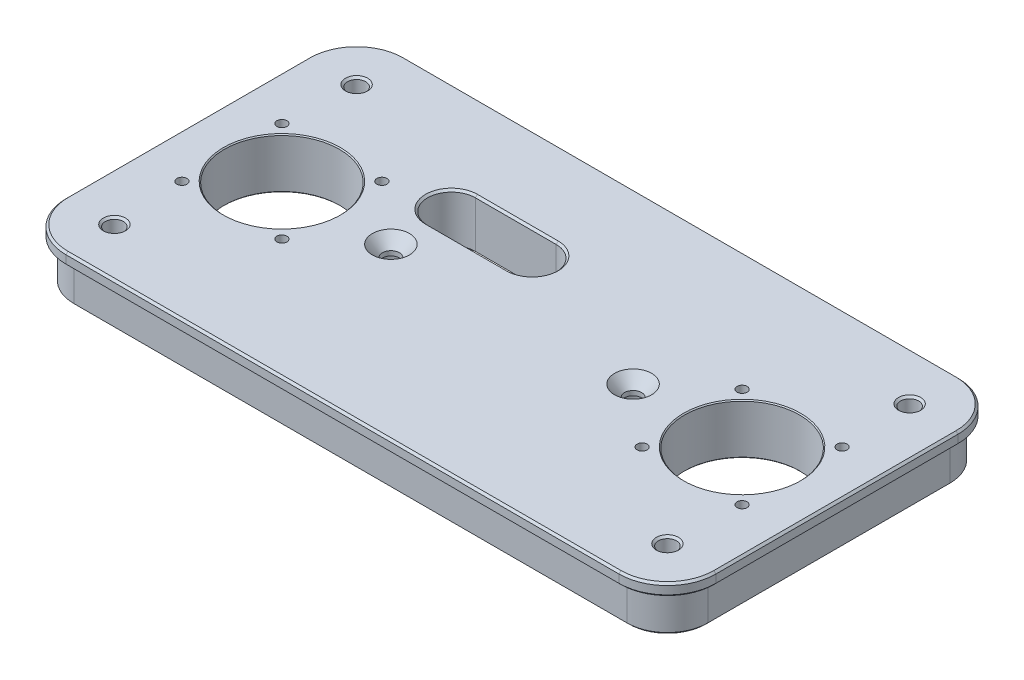
SolidWorks part; units mm, degrees
material "6061-T6 Aluminum"
ref_plane "Front Plane" through (0, 0, 0) normal (0, 0, 1) x (1, 0, 0)
ref_plane "Top Plane" through (0, 0, 0) normal (0, 1, 0) x (1, 0, 0)
ref_plane "Right Plane" through (0, 0, 0) normal (1, 0, 0) x (0, 0, -1)
sketch "Sketch1" plane through (0, 0, 0) normal (0, 1, 0) x (1, 0, 0)
  line L1 (-157, -80) -> (157, -80)
  line L2 (-157, -80) -> (-157, 80)
  line L3 (-157, 80) -> (157, 80)
  line L4 (157, -80) -> (157, 80)
  line L5 (-157, -80) -> (157, 80) construction
  line L6 (-157, 80) -> (157, -80) construction
  point P0 (0, 0)
  dimension "D1" = 160
  dimension "D2" = 314
extrude "Boss-Extrude1" add sketch "Sketch1" along normal blind 25
sketch "Sketch2" plane through (0, 25, 0) normal (0, 1, 0) x (1, 0, 0)
  line L0 (-114, 0) -> (0, 0) construction
  line L1 (0, 0) -> (114, 0) construction
  circle A0 centre (-114, 0) radius 28.5
  circle A1 centre (114, 0) radius 28.5
  dimension "D1" = 228
  dimension "D2" = 57
extrude "Cut-Extrude1" cut sketch "Sketch2" against normal through all
sketch "Sketch4" plane through (0, 25, 0) normal (0, 1, 0) x (1, 0, 0)
  line L0 (60, 0) -> (0, 0) construction
  line L1 (0, 0) -> (-60, 0) construction
  circle A0 centre (-60, 0) radius 9.55
  circle A1 centre (60, 0) radius 9.55
  dimension "D1" = 19.1
  dimension "D2" = 120
extrude "Cut-Extrude2" cut sketch "Sketch4" against normal through all both and the other way through all
chamfer "Chamfer1" distance 0.5 angle 45 8 edges at (114, 25, 28.5) (114, 0, 28.5) (60, 25, -9.55) (60, 0, 9.55) (-60, 25, -9.55) (-60, 0, 9.55) (-114, 25, 28.5) (-114, 0, 28.5)
fillet "Fillet1" radius 20 4 edges at (157, 12.5, 80) (157, 12.5, -80) (-157, 12.5, -80) (-157, 12.5, 80)
hole_wizard "M8 Clearance Hole1" positions "Sketch5" profile "Sketch6" hole size "M8" standard "ANSI Metric" end condition through all
sketch "Sketch5" plane through (0, 0, 0) normal (0, 1, 0) x (1, 0, 0)
  point P0 (-137, 60)
  point P3 (-137, -60)
  point P6 (137, 60)
  point P9 (137, -60)
sketch "Sketch6" plane through (-137, 0, -60) normal (1, 0, 0) x (0, 0, -1)
  line L0 (0, 0) -> (0, 25)
  line L1 (0, 25) -> (4.5, 25)
  line L2 (4.5, 25) -> (4.5, 0)
  line L5 (4.5, 0) -> (0, 0)
  line L11 (0, -6.35) -> (0, 107.95) construction
  dimension "Thru Hole Dia." = 9
  dimension "Thru Hole Depth" = 25
sketch "Sketch7" plane through (0, 0, 0) normal (0, -1, 0) x (1, 0, 0)
  line L1 (89.235, 24.765) -> (138.765, 24.765) construction
  line L2 (89.235, 24.765) -> (89.235, -24.765) construction
  line L3 (89.235, -24.765) -> (138.765, -24.765) construction
  line L4 (138.765, 24.765) -> (138.765, -24.765) construction
  line L5 (89.235, 24.765) -> (138.765, -24.765) construction
  line L6 (89.235, -24.765) -> (138.765, 24.765) construction
  line L7 (-138.765, 24.765) -> (-89.235, 24.765) construction
  line L8 (-138.765, 24.765) -> (-138.765, -24.765) construction
  line L9 (-138.765, -24.765) -> (-89.235, -24.765) construction
  line L10 (-89.235, 24.765) -> (-89.235, -24.765) construction
  line L11 (-138.765, 24.765) -> (-89.235, -24.765) construction
  line L12 (-138.765, -24.765) -> (-89.235, 24.765) construction
  circle A0 centre (89.235, 24.765) radius 3.302 construction
  circle A1 centre (138.765, -24.765) radius 3.302 construction
  circle A2 centre (138.765, 24.765) radius 3.302 construction
  circle A3 centre (89.235, -24.765) radius 3.302 construction
  circle A4 centre (89.235, 24.765) radius 3.302
  circle A5 centre (138.765, -24.765) radius 3.302
  circle A6 centre (138.765, 24.765) radius 3.302
  circle A7 centre (89.235, -24.765) radius 3.302
  circle A12 centre (-138.765, -24.765) radius 3.302
  circle A13 centre (-89.235, -24.765) radius 3.302
  circle A14 centre (-89.235, 24.765) radius 3.302
  circle A15 centre (-138.765, 24.765) radius 3.302
  point P13 (114, 0)
  point P15 (-114, 0)
hole_wizard "M6x1.0 Tapped Hole1" positions "Sketch8" profile "Sketch9" tap size "M6x1.0" standard "ANSI Metric" end condition through all
sketch "Sketch8" plane through (0, 0, 0) normal (0, -1, 0) x (-1, 0, 0)
  point P0 (138.765, -24.765)
  point P3 (89.235, -24.765)
  point P6 (89.235, 24.765)
  point P9 (138.765, 24.765)
  point P12 (-89.235, -24.765)
  point P15 (-138.765, -24.765)
  point P18 (-89.235, 24.765)
  point P21 (-138.765, 24.765)
cosmetic thread "Hole Thread11" parameters "D2"=6
cosmetic thread "Hole Thread12" parameters "D2"=6
cosmetic thread "Hole Thread13" parameters "D2"=6
cosmetic thread "Hole Thread14" parameters "D2"=6
cosmetic thread "Hole Thread16" parameters "D2"=6
sketch "Sketch9" plane through (-138.765, 0, 24.765) normal (1, 0, 0) x (0, 0, -1)
  line L0 (0, 0) -> (0, 25)
  line L1 (0, 25) -> (2.5, 25)
  line L2 (2.5, 25) -> (2.5, 0)
  line L5 (2.5, 0) -> (0, 0)
  line L11 (0, -6.35) -> (0, 107.95) construction
  dimension "Thru Tap Drill Dia." = 5
  dimension "Thru Tap Drill Depth" = 25
cosmetic thread "Hole Thread17" parameters "D2"=6
cosmetic thread "Hole Thread18" parameters "D2"=6
cosmetic thread "Hole Thread19" parameters "D2"=6
sketch "Sketch13" plane through (0, 25, 0) normal (0, 1, 0) x (1, 0, 0)
  circle A0 centre (60, 0) radius 13.411
  circle A1 centre (-60, 0) radius 14.7245
extrude "Boss-Extrude3" add sketch "Sketch13" against normal blind 8
hole_wizard "CSK for 5/16 Flat Head Socket Cap Screw1" positions "Sketch14" profile "Sketch15" countersink size "5/16" standard "ANSI Inch" end condition through all
sketch "Sketch14" plane through (0, 25, 0) normal (0, 1, 0) x (1, 0, 0)
  point P0 (60, 0)
  point P3 (-60, 0)
sketch "Sketch15" plane through (60, 25, 0) normal (1, 0, 0) x (0, 0, 1)
  line L0 (0, 0) -> (0, 25)
  line L1 (0, 25) -> (4.2164, 25)
  line L2 (4.2164, 25) -> (4.2164, 5.7335)
  line L3 (4.2164, 5.7335) -> (9.2005, 0)
  line L5 (9.2005, 0) -> (0, 0)
  line L6 (-4.2164, 5.7335) -> (-9.2005, 0) construction
  line L11 (0, -6.35) -> (0, 107.95) construction
  dimension "Thru Hole Dia." = 8.4328
  dimension "Thru Hole Depth" = 25
  dimension "Near C'Sink Dia." = 18.401
  dimension "Near C'Sink Angle" = 82
sketch "Sketch16" plane through (0, 25, 0) normal (0, -1, 0) x (1, 0, 0)
  line L4 (157, 60) -> (157, -60) construction
  line L5 (137, -80) -> (-137, -80) construction
  line L6 (-157, -60) -> (-157, 60) construction
  line L7 (-137, 80) -> (137, 80) construction
  line L8 (161, -60) -> (161, 60)
  line L9 (137, 84) -> (-137, 84)
  line L10 (-161, 60) -> (-161, -60)
  line L11 (-137, -84) -> (137, -84)
  line L12 (161, -60) -> (161, 60)
  line L13 (137, 84) -> (-137, 84)
  line L14 (-161, 60) -> (-161, -60)
  line L15 (-137, -84) -> (137, -84)
  line L16 (157, 60) -> (157, -60)
  line L17 (137, -80) -> (-137, -80)
  line L18 (-157, -60) -> (-157, 60)
  line L19 (-137, 80) -> (137, 80)
  arc A4 (157, 60) -> (137, 80) centre (137, 60) ccw construction
  arc A5 (137, -80) -> (157, -60) centre (137, -60) ccw construction
  arc A6 (-157, -60) -> (-137, -80) centre (-137, -60) ccw construction
  arc A7 (-137, 80) -> (-157, 60) centre (-137, 60) ccw construction
  arc A8 (161, 60) -> (137, 84) centre (137, 60) ccw
  arc A9 (-137, 84) -> (-161, 60) centre (-137, 60) ccw
  arc A10 (-161, -60) -> (-137, -84) centre (-137, -60) ccw
  arc A11 (137, -84) -> (161, -60) centre (137, -60) ccw
  arc A12 (161, 60) -> (137, 84) centre (137, 60) ccw
  arc A13 (-137, 84) -> (-161, 60) centre (-137, 60) ccw
  arc A14 (-161, -60) -> (-137, -84) centre (-137, -60) ccw
  arc A15 (137, -84) -> (161, -60) centre (137, -60) ccw
  arc A16 (157, 60) -> (137, 80) centre (137, 60) ccw
  arc A17 (137, -80) -> (157, -60) centre (137, -60) ccw
  arc A18 (-157, -60) -> (-137, -80) centre (-137, -60) ccw
  arc A19 (-137, 80) -> (-157, 60) centre (-137, 60) ccw
  dimension "D1" = 4
extrude "Boss-Extrude4" add sketch "Sketch16" along normal blind 6
sketch "Sketch17" plane through (0, 0, 0) normal (0, -1, 0) x (1, 0, 0)
  line L0 (-60, -30.0192) -> (-20, -30.0192) construction
  line L1 (-60, -18.1841) -> (-20, -18.1841)
  line L2 (-60, -41.8544) -> (-20, -41.8544)
  circle A0 centre (-60, -30.0192) radius 9.2363 construction
  arc A1 (-69.9426, -35.7596) -> (-50.0574, -35.7596) centre (-60, -30.0192) ccw construction
  arc A2 (-60, -18.1841) -> (-60, -41.8544) centre (-60, -30.0192) ccw
  arc A3 (-20, -41.8544) -> (-20, -18.1841) centre (-20, -30.0192) ccw
  point P2 (-40, -30.0192)
  point P11 (-60.4895, -18.1942)
  dimension "D1" = 40
extrude "Cut-Extrude3" cut sketch "Sketch17" against normal through all
chamfer "Chamfer4" distance 1 angle 45 40 edges at (137, 0, -64.5) (137, 25, -64.5) (-137, 0, -64.5) (-137, 25, -64.5) (137, 0, 55.5) (137, 25, 55.5) (-137, 0, 55.5) (-137, 25, 55.5) (0, 19, -84) (153.9706, 19, -76.9706) (-153.9706, 19, -76.9706) (161, 19, 0) (-161, 19, 0) (153.9706, 19, 76.9706) (-153.9706, 19, 76.9706) (0, 19, 84) (0, 25, -84) (153.9706, 25, -76.9706) (-153.9706, 25, -76.9706) (161, 25, 0) (-161, 25, 0) (153.9706, 25, 76.9706) (-153.9706, 25, 76.9706) (0, 25, 84) (-40, 25, -18.1841) (-71.8351, 25, -30.0192) (-8.1649, 25, -30.0192) (-40, 25, -41.8544) (-40, 0, -18.1841) (-71.8351, 0, -30.0192) (-8.1649, 0, -30.0192) (-40, 0, -41.8544) (0, 0, -80) (-151.1421, 0, -74.1421) (151.1421, 0, -74.1421) (-157, 0, 0) (157, 0, 0) (-151.1421, 0, 74.1421) (151.1421, 0, 74.1421) (0, 0, 80)
